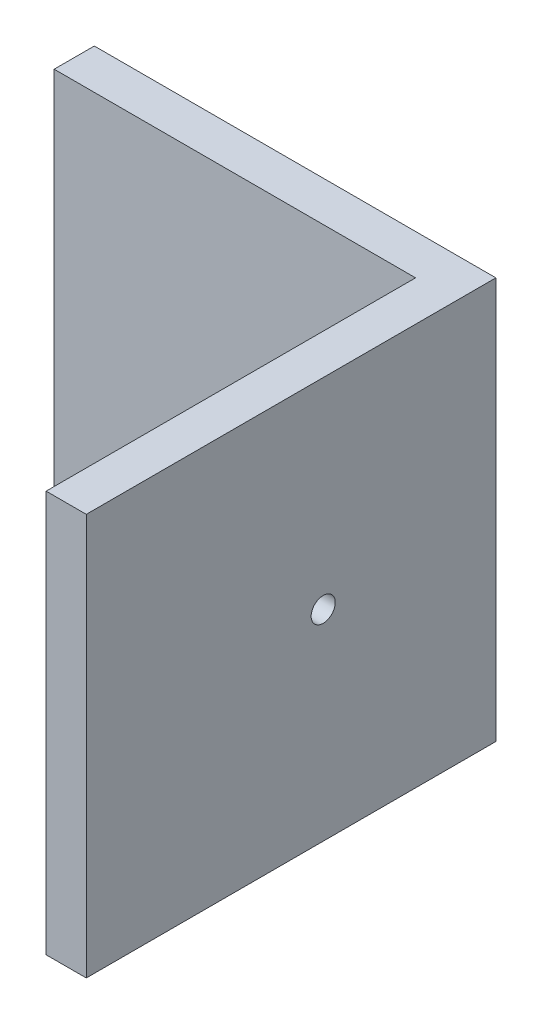
SolidWorks part; units mm, degrees
ref_plane "正面" through (0, 0, 0) normal (0, 0, 1) x (1, 0, 0)
ref_plane "平面" through (0, 0, 0) normal (0, 1, 0) x (1, 0, 0)
ref_plane "右側面" through (0, 0, 0) normal (1, 0, 0) x (0, 0, -1)
sketch "ｽｹｯﾁ1" plane through (0, 0, 0) normal (0, 0, 1) x (1, 0, 0)
  line L0 (0, 0) -> (20, 0)
  line L1 (-25, -25) -> (25, -25)
  line L2 (-25, -25) -> (-25, 25)
  line L3 (-25, 25) -> (25, 25)
  line L4 (25, -25) -> (25, 25)
  line L5 (-25, -25) -> (25, 25) construction
  line L6 (-25, 25) -> (25, -25) construction
  line L7 (25, 25) -> (20, 25)
  line L8 (25, 25) -> (25, -25)
  line L9 (25, -25) -> (20, -25)
  line L10 (20, 25) -> (20, -25)
  circle A0 centre (9.5, 0) radius 1.5
  point P0 (0, 0)
  dimension "D4" = 3
  dimension "D5" = 10.5
  dimension "D1" = 50
  dimension "D2" = 50
  dimension "D3" = 5
extrude "ﾎﾞｽ - 押し出し1" add sketch "ｽｹｯﾁ1" along normal blind 5 contours L10 L3 L2 L1 region at (-2.5378, 0, 0)
extrude "ﾎﾞｽ - 押し出し2" add sketch "ｽｹｯﾁ1<4>" along normal blind 51 contours L3 L10 L1 L4 region at (22.5, 0, 0)
sketch "ｽｹｯﾁ1<4>" plane through (0, 0, 0) normal (0, 0, 1) x (1, 0, 0) same geometry as "ｽｹｯﾁ1"
sketch "ｽｹｯﾁ2" plane through (20, 0, 0) normal (-1, 0, 0) x (0, 0, 1)
  line L0 (51, 0) -> (5, 0)
  line L1 (51, 25) -> (51, -25) construction
  line L2 (5, -25) -> (5, 25) construction
  circle A0 centre (21.5, 0) radius 1.5
  dimension "D1" = 3
  dimension "D2" = 16.5
extrude "ｶｯﾄ - 押し出し1" cut sketch "ｽｹｯﾁ2" against normal blind 10 contours L0 A0 | L0 A0 region at (20, -0.6366, 21.5) region at (20, 0.6366, 21.5)
